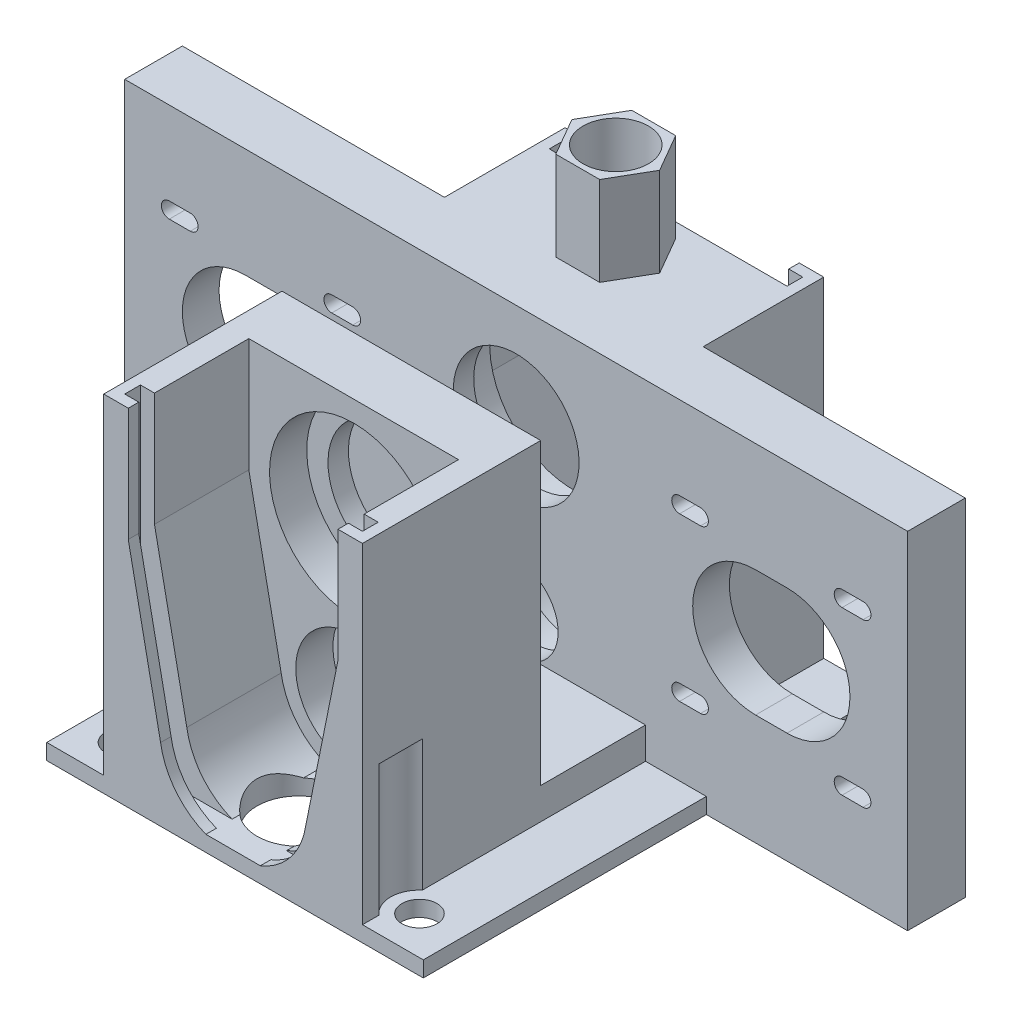
SolidWorks part; units mm, degrees
ref_plane "Front Plane" through (0, 0, 0) normal (0, 0, 1) x (1, 0, 0)
ref_plane "Top Plane" through (0, 0, 0) normal (0, 1, 0) x (1, 0, 0)
ref_plane "Right Plane" through (0, 0, 0) normal (1, 0, 0) x (0, 0, -1)
ref_axis "Axis1" through (88.99, 0, 0) along (-1, 0, 0)
ref_plane "Plane1" through (0, 0, 0) normal (0, 0, -1) x (-1, 0, 0)
ref_plane "Plane2" through (0, 0, 0) normal (0, -1, 0) x (-1, 0, 0)
ref_plane "Plane3" through (0, 0, -42) normal (0, 0, -1) x (-1, 0, 0)
sketch "Sketch2" plane through (0, 0, 0) normal (0, 0, -1) x (-1, 0, 0)
  line L2 (0, 58.0413) -> (0, 28.0413) construction
  line L3 (-24.6785, 78.0413) -> (24.6785, 78.0413)
  line L4 (57.5751, 12.0413) -> (-72.0682, 12.0413) construction
  line L5 (-24.6785, 78.0413) -> (-24.6785, 12.0413)
  line L6 (-24.6785, 12.0413) -> (24.6785, 12.0413)
  line L7 (24.6785, 12.0413) -> (24.6785, 78.0413)
  circle A0 centre (0, 28.0413) radius 11 construction
  circle A1 centre (0, 58.0413) radius 16 construction
  point P4 (0, 58.0413)
  point P6 (0, 28.0413)
  point P7 (20.0824, 64.1811)
  point P8 (15.3009, 32.7193)
  dimension "D1" = 32
  dimension "D2" = 22
  dimension "D6" = 66
  dimension "D3" = 30
  dimension "D5" = 20
  dimension "D4" = 16
extrude "Boss-Extrude1" add sketch "Sketch2" along normal blind 65
ref_plane "Plane5" through (0, 12.0413, 0) normal (0, -1, 0) x (-1, 0, 0)
sketch "Sketch3" plane through (0, 0, 0) normal (0, 0, -1) x (-1, 0, 0)
  line L0 (-24.6785, 12.0413) -> (24.6785, 12.0413) construction
  line L1 (0, 0) -> (0, 102.6324) construction
  circle A0 centre (0, 28.0413) radius 8
  circle A1 centre (0, 58.0413) radius 12
  circle A3 centre (0, 58.0413) radius 16 construction
  circle A4 centre (0, 28.0413) radius 11 construction
  dimension "D1" = 4
  dimension "D2" = 3
  dimension "D4" = 16
  dimension "D5" = 22
  dimension "D6" = 32
  dimension "D3" = 30
extrude "Cut-Extrude1" cut sketch "Sketch3" along normal blind 42
sketch "Sketch5" plane through (0, 0, -42) normal (0, 0, -1) x (-1, 0, 0)
  line L2 (-20, 76.0413) -> (20, 76.0413)
  line L4 (-24.6785, 12.0413) -> (24.6785, 12.0413) construction
  line L6 (13.8042, 25.708) -> (20, 49.5058)
  line L7 (-20, 49.5726) -> (-13.8042, 25.708)
  line L10 (24.6785, 78.0413) -> (-24.6785, 78.0413) construction
  line L11 (-20, 76.0413) -> (-20, 49.5726)
  line L12 (20, 76.0413) -> (20, 49.5058)
  circle A1 centre (0, 58.0413) radius 16 construction
  arc A3 (-13.8042, 25.708) -> (13.8042, 25.708) centre (0, 28.0413) ccw
  dimension "D2" = 16
  dimension "D1" = 14
  dimension "D6" = 32
  dimension "D5" = 2
  dimension "D7" = 30
  dimension "D8" = 20
  dimension "D9" = 20
extrude "Cut-Extrude2" cut sketch "Sketch5" along normal through all
sketch "Sketch6" plane through (0, 0, 0) normal (0, 0, -1) x (-1, 0, 0)
  circle A0 centre (0, 58.0413) radius 16.05
  circle A1 centre (0, 58.0413) radius 12 construction
  circle A2 centre (0, 28.0413) radius 11.05
  circle A3 centre (0, 28.0413) radius 8 construction
  dimension "D1" = 32.1
  dimension "D2" = 22.1
extrude "Cut-Extrude3" cut sketch "Sketch6" along normal blind 7.1
sketch "Sketch7" plane through (0, 0, -42) normal (0, 0, -1) x (-1, 0, 0)
  circle A2 centre (0, 58.0413) radius 16.05
  circle A3 centre (0, 58.0413) radius 16.05
  circle A5 centre (0, 28.0413) radius 11.05
  circle A6 centre (0, 28.0413) radius 11.05
  dimension "D1" = 0
  dimension "D2" = 0
extrude "Cut-Extrude4" cut sketch "Sketch7" against normal blind 7.1
sketch "Sketch8" plane through (0, 0, 0) normal (0, 0, -1) x (-1, 0, 0)
  line L2 (24.6785, 78.0413) -> (-24.6785, 78.0413)
  line L3 (24.6785, 78.0413) -> (24.6785, 12.0413)
  line L4 (24.6785, 12.0413) -> (-24.6785, 12.0413)
  line L5 (-24.6785, 12.0413) -> (-24.6785, 78.0413)
extrude "Boss-Extrude2" add sketch "Sketch8" against normal blind 23
sketch "Sketch9" plane through (0, 0, 0) normal (0, 0, -1) x (-1, 0, 0)
  line L2 (20, 78.0413) -> (-20, 78.0413)
  line L4 (-24.6785, 12.0413) -> (24.6785, 12.0413) construction
  line L5 (20, 78.0413) -> (20, 56.3516)
  line L6 (-20, 56.3516) -> (-13.8326, 25.8825)
  line L7 (13.8326, 25.8825) -> (20, 56.3516)
  line L8 (-20, 78.0413) -> (-20, 56.3516)
  circle A0 centre (0, 56.2822) radius 16 construction
  arc A3 (-13.8326, 25.8825) -> (13.8326, 25.8825) centre (0, 28.0413) ccw
  dimension "D1" = 14
  dimension "D5" = 32
  dimension "D2" = 16
  dimension "D6" = 20
  dimension "D7" = 20
extrude "Cut-Extrude5" cut sketch "Sketch9" against normal through all
ref_plane "Plane4" through (0, 0, -31) normal (0, 0, -1) x (-1, 0, 0)
sketch "Sketch10" plane through (0, 0, -31) normal (0, 0, -1) x (-1, 0, 0)
  line L1 (32.0175, 70.0413) -> (32.0175, 29.2185)
  line L2 (-24.6785, 12.0413) -> (24.6785, 12.0413) construction
  line L5 (-28.9461, 62.8412) -> (-28.9461, 21.0413)
  line L8 (0.9045, 21.0413) -> (-28.9461, 21.0413)
  line L9 (0, 0) -> (0, 85.4363) construction
  line L10 (0.9045, 21.0413) -> (32.0175, 29.2185)
  line L12 (-28.9461, 62.8412) -> (-28.9461, 84.6224)
  line L13 (-28.9461, 84.6224) -> (32.0175, 84.6224)
  line L14 (32.0175, 84.6224) -> (32.0175, 70.0413)
  circle A0 centre (0, 58.0413) radius 10 construction
  circle A1 centre (0, 58.0413) radius 16 construction
  circle A2 centre (0, 28.0413) radius 11 construction
  circle A4 centre (0, 28.0413) radius 4 construction
  dimension "D1" = 32
  dimension "D2" = 22
  dimension "D3" = 30
  dimension "D4" = 20
  dimension "D5" = 8
  dimension "D6" = 16
  dimension "D7" = 7
  dimension "D10" = 7
extrude "Cut-Extrude6" cut sketch "Sketch10" against normal blind 20
sketch "Sketch12" plane through (0, 0, 0) normal (0, 1, 0) x (1, 0, 0)
  circle A0 centre (0, -10.444) radius 8
  ellipse E0 centre (0, -2.444) end of major axis (14, -2.444) minor radius 1.2202 (13.8326, -2.2558) -> (-13.8326, -2.2558) ccw construction
  dimension "D1" = 16
  dimension "D2" = 8
extrude "Cut-Extrude8" cut sketch "Sketch12" along normal up to surface (14.0413 mm away) up to face at (0, 19.9619, 11.5)
sketch "Sketch13" plane through (0, 12.0413, 0) normal (0, -1, 0) x (-1, 0, 0)
  line L2 (24.6785, 11) -> (24.6785, 31)
  line L3 (24.6785, 11) -> (24.6785, 31) construction
  line L4 (24.6785, 31) -> (24.6785, 42)
  line L5 (-24.6785, 65) -> (24.6785, 65) construction
  line L7 (24.6785, 42) -> (74.6785, 42)
  line L8 (97.889, 42) -> (-97.889, 42) construction
  line L9 (74.6785, 42) -> (74.6785, 31)
  line L10 (97.889, 31) -> (-97.889, 31) construction
  line L11 (74.6785, 31) -> (24.6785, 31)
  line L12 (-24.6785, 42) -> (-74.6785, 42)
  line L13 (-24.6785, 65) -> (-24.6785, -23) construction
  line L14 (-74.6785, 42) -> (-74.6785, 31)
  line L15 (-74.6785, 31) -> (-24.6785, 31)
  line L16 (-24.6785, 31) -> (-24.6785, 42)
  dimension "D3" = 50
  dimension "D2" = 23
  dimension "D1" = 0
extrude "Boss-Extrude3" add sketch "Sketch13" against normal up to surface (66 mm away) up to face at (0, 78.0413, -48)
sketch "Sketch15" plane through (0, 0, -42) normal (0, 0, -1) x (-1, 0, 0)
  line L0 (0, 0) -> (0, 87.2744) construction
  line L1 (74.6785, 78.0413) -> (74.6785, 12.0413) construction
  line L2 (25.6785, 66.3413) -> (71.6785, 66.3413)
  line L3 (25.6785, 66.3413) -> (25.6785, 24.0413)
  line L4 (25.6785, 24.0413) -> (71.6785, 24.0413)
  line L5 (71.6785, 66.3413) -> (71.6785, 24.0413)
  line L6 (24.6785, 12.0413) -> (24.6785, 78.0413) construction
  line L7 (-27.1464, 12.0413) -> (27.1464, 12.0413) construction
  line L8 (-71.6785, 66.3413) -> (-71.6785, 24.0413)
  line L9 (-25.6785, 24.0413) -> (-71.6785, 24.0413)
  line L10 (-25.6785, 66.3413) -> (-25.6785, 24.0413)
  line L11 (-25.6785, 66.3413) -> (-71.6785, 66.3413)
  dimension "D1" = 3
  dimension "D2" = 1
  dimension "D3" = 42.3
  dimension "D4" = 12
extrude "Cut-Extrude9" cut sketch "Sketch15" against normal blind 4
sketch "Sketch16" plane through (0, 0, -42) normal (0, 0, -1) x (-1, 0, 0)
  line L0 (-105.1978, 45.1913) -> (88.1587, 45.1913) construction
  line L1 (71.6785, 66.3413) -> (25.6785, 66.3413) construction
  line L2 (25.6785, 24.0413) -> (71.6785, 24.0413) construction
  line L3 (45.6785, 45.1913) -> (51.6785, 45.1913) construction
  line L4 (45.6785, 57.1913) -> (51.6785, 57.1913)
  line L5 (45.6785, 33.1913) -> (51.6785, 33.1913)
  line L6 (48.6785, 83.554) -> (48.6785, 16.5047) construction
  line L7 (25.6785, 66.3413) -> (25.6785, 24.0413) construction
  line L8 (71.6785, 24.0413) -> (71.6785, 66.3413) construction
  line L9 (31.1785, 60.6913) -> (35.1785, 60.6913) construction
  line L10 (31.1785, 62.1913) -> (35.1785, 62.1913)
  line L11 (31.1785, 59.1913) -> (35.1785, 59.1913)
  line L12 (66.1785, 60.6913) -> (62.1785, 60.6913) construction
  line L25 (66.1785, 62.1913) -> (62.1785, 62.1913)
  line L26 (66.1785, 59.1913) -> (62.1785, 59.1913)
  line L27 (31.1785, 29.6913) -> (35.1785, 29.6913) construction
  line L28 (31.1785, 28.1913) -> (35.1785, 28.1913)
  line L29 (31.1785, 31.1913) -> (35.1785, 31.1913)
  line L30 (66.1785, 29.6913) -> (62.1785, 29.6913) construction
  line L31 (66.1785, 28.1913) -> (62.1785, 28.1913)
  line L32 (66.1785, 31.1913) -> (62.1785, 31.1913)
  line L33 (0, 0) -> (0, 89.9864) construction
  line L34 (-45.6785, 45.1913) -> (-51.6785, 45.1913) construction
  line L35 (-45.6785, 57.1913) -> (-51.6785, 57.1913)
  line L36 (-45.6785, 33.1913) -> (-51.6785, 33.1913)
  line L37 (-31.1785, 60.6913) -> (-35.1785, 60.6913) construction
  line L38 (-31.1785, 62.1913) -> (-35.1785, 62.1913)
  line L39 (-31.1785, 59.1913) -> (-35.1785, 59.1913)
  line L40 (-66.1785, 60.6913) -> (-62.1785, 60.6913) construction
  line L41 (-66.1785, 62.1913) -> (-62.1785, 62.1913)
  line L42 (-66.1785, 59.1913) -> (-62.1785, 59.1913)
  line L43 (-31.1785, 29.6913) -> (-35.1785, 29.6913) construction
  line L44 (-31.1785, 28.1913) -> (-35.1785, 28.1913)
  line L45 (-31.1785, 31.1913) -> (-35.1785, 31.1913)
  line L46 (-66.1785, 29.6913) -> (-62.1785, 29.6913) construction
  line L47 (-66.1785, 28.1913) -> (-62.1785, 28.1913)
  line L48 (-66.1785, 31.1913) -> (-62.1785, 31.1913)
  arc A0 (45.6785, 57.1913) -> (45.6785, 33.1913) centre (45.6785, 45.1913) ccw
  arc A1 (51.6785, 33.1913) -> (51.6785, 57.1913) centre (51.6785, 45.1913) ccw
  arc A2 (31.1785, 62.1913) -> (31.1785, 59.1913) centre (31.1785, 60.6913) ccw
  arc A3 (35.1785, 59.1913) -> (35.1785, 62.1913) centre (35.1785, 60.6913) ccw
  arc A16 (66.1785, 62.1913) -> (66.1785, 59.1913) centre (66.1785, 60.6913) cw
  arc A17 (62.1785, 59.1913) -> (62.1785, 62.1913) centre (62.1785, 60.6913) cw
  arc A18 (31.1785, 28.1913) -> (31.1785, 31.1913) centre (31.1785, 29.6913) cw
  arc A19 (35.1785, 31.1913) -> (35.1785, 28.1913) centre (35.1785, 29.6913) cw
  arc A20 (66.1785, 28.1913) -> (66.1785, 31.1913) centre (66.1785, 29.6913) ccw
  arc A21 (62.1785, 31.1913) -> (62.1785, 28.1913) centre (62.1785, 29.6913) ccw
  arc A22 (-45.6785, 57.1913) -> (-45.6785, 33.1913) centre (-45.6785, 45.1913) cw
  arc A23 (-51.6785, 33.1913) -> (-51.6785, 57.1913) centre (-51.6785, 45.1913) cw
  arc A24 (-31.1785, 62.1913) -> (-31.1785, 59.1913) centre (-31.1785, 60.6913) cw
  arc A25 (-35.1785, 59.1913) -> (-35.1785, 62.1913) centre (-35.1785, 60.6913) cw
  arc A26 (-66.1785, 62.1913) -> (-66.1785, 59.1913) centre (-66.1785, 60.6913) ccw
  arc A27 (-62.1785, 59.1913) -> (-62.1785, 62.1913) centre (-62.1785, 60.6913) ccw
  arc A28 (-31.1785, 28.1913) -> (-31.1785, 31.1913) centre (-31.1785, 29.6913) ccw
  arc A29 (-35.1785, 31.1913) -> (-35.1785, 28.1913) centre (-35.1785, 29.6913) ccw
  arc A30 (-66.1785, 28.1913) -> (-66.1785, 31.1913) centre (-66.1785, 29.6913) cw
  arc A31 (-62.1785, 31.1913) -> (-62.1785, 28.1913) centre (-62.1785, 29.6913) cw
  point P8 (48.6785, 45.1913)
  point P14 (33.1785, 60.6913)
  point P28 (64.1785, 60.6913)
  point P36 (33.1785, 29.6913)
  point P43 (64.1785, 29.6913)
  point P52 (-48.6785, 45.1913)
  point P59 (-33.1785, 60.6913)
  point P66 (-64.1785, 60.6913)
  point P73 (-33.1785, 29.6913)
  point P80 (-64.1785, 29.6913)
  dimension "D1" = 12
  dimension "D3" = 31
  dimension "D4" = 1.5
  dimension "D2" = 31
  dimension "D5" = 4
  dimension "D6" = 6
extrude "Cut-Extrude10" cut sketch "Sketch16" against normal up to next
sketch "Sketch17" plane through (0, 78.0413, 0) normal (0, 1, 0) x (1, 0, 0)
  line L0 (0, 55.3583) -> (0, 85.749) construction
  line L1 (-35.5458, 50) -> (45.8299, 50) construction
  line L4 (97.889, 42) -> (-97.889, 42) construction
  line L5 (8.3716, 50) -> (4.1858, 57.25)
  line L6 (4.1858, 57.25) -> (-4.1858, 57.25)
  line L7 (-4.1858, 57.25) -> (-8.3716, 50)
  line L8 (-8.3716, 50) -> (-4.1858, 42.75)
  line L9 (-4.1858, 42.75) -> (4.1858, 42.75)
  line L10 (4.1858, 42.75) -> (8.3716, 50)
  circle A0 centre (0, 50) radius 7.25 construction
  circle A1 centre (0, 50) radius 6.25
  dimension "D2" = 12.5
  dimension "D1" = 14.5
  dimension "D3" = 8
extrude "Boss-Extrude4" add sketch "Sketch17" along normal blind 17
sketch "Sketch18" plane through (0, 78.0413, 0) normal (0, 1, 0) x (1, 0, 0)
  circle A2 centre (0, 50) radius 6.25
  circle A3 centre (0, 50) radius 6.25
  dimension "D1" = 0
extrude "Cut-Extrude11" cut sketch "Sketch18" against normal up to next
sketch "Sketch19" plane through (0, 12.0413, 0) normal (0, -1, 0) x (-1, 0, 0)
  line L0 (-66.3049, 12.556) -> (66.3049, 12.556) construction
  line L1 (0, 76.6155) -> (0, 65) construction
  line L2 (-61.7241, 74.2802) -> (0.6987, 11.8573) construction
  line L4 (13.4481, 26.0042) -> (0, 12.556) construction
  line L7 (-36.2843, 48.8403) -> (-36.2843, -23)
  line L9 (35.556, 48.8403) -> (35.556, -23)
  line L10 (-36.2843, 48.8403) -> (-36.2843, 65)
  line L12 (35.556, 65) -> (35.556, 48.8403)
  line L27 (0, 42) -> (0, -57.588) construction
  line L28 (-25.9179, -13.3619) -> (-763.264, -750.708) construction
  line L29 (-36.2843, 65) -> (35.556, 65)
  line L30 (-36.2843, -23) -> (35.556, -23)
  circle A3 centre (-28.2843, 40.8403) radius 3.3465
  circle A6 centre (28.2843, 40.8403) radius 3.3465
  circle A7 centre (-28.2843, -15.7282) radius 3.3465
  circle A8 centre (28.2843, -15.7282) radius 3.3465
  circle A10 centre (0, -10.444) radius 8
  circle A11 centre (0, -10.444) radius 8
  point P3 (0, 12.556)
  dimension "D2" = 45
  dimension "D1" = 45
  dimension "D5" = 40
  dimension "D6" = 8
  dimension "D3" = 0
extrude "Boss-Extrude5" add sketch "Sketch19" against normal blind 3
sketch "Sketch20" plane through (0, 15.0413, 0) normal (0, 1, 0) x (1, 0, 0)
  circle A0 centre (-28.2843, -15.7282) radius 5.5
  circle A1 centre (28.2843, -15.7282) radius 5.5
  circle A2 centre (28.2843, 40.8403) radius 5.5
  circle A3 centre (-28.2843, 40.8403) radius 5.5
  dimension "D1" = 11
extrude "Cut-Extrude12" cut sketch "Sketch20" along normal blind 25
sketch "Sketch21" plane through (0, 12.0413, 0) normal (0, -1, 0) x (-1, 0, 0)
  circle A0 centre (-28.2843, 40.8403) radius 3.3465
  arc A1 (-25.1451, 42) -> (-31.4234, 42) centre (-28.2843, 40.8403) ccw construction
  circle A2 centre (28.2843, 40.8403) radius 3.3465
  arc A3 (31.4234, 42) -> (25.1451, 42) centre (28.2843, 40.8403) ccw construction
extrude "Cut-Extrude13" cut sketch "Sketch21" against normal up to next
sketch "Sketch22" plane through (0, 0, 0) normal (1, 0, 0) x (0, 0, -1)
  line L0 (63, 78.0413) -> (63, 15.0413)
  line L3 (65, 78.0413) -> (42, 78.0413) construction
  line L7 (44.9934, 15.0413) -> (65, 15.0413) construction
  line L8 (63, 15.0413) -> (65, 15.0413)
  line L9 (65, 78.0413) -> (65, 15.0413) construction
  line L10 (-21, 81.0679) -> (-21, 15.0413)
  line L12 (-23, 15.0413) -> (-19.8814, 15.0413) construction
  line L13 (-21, 15.0413) -> (-23, 15.0413)
  line L14 (-23, 78.0413) -> (-23, 15.0413) construction
  dimension "D1" = 2
  dimension "D2" = 2
sketch "Sketch23" plane through (0, 78.0413, 0) normal (0, 1, 0) x (1, 0, 0)
  line L0 (-24.6785, 65) -> (24.6785, 65) construction
  line L1 (-22.6785, 63) -> (22.6785, 63)
  line L2 (-22.6785, 63) -> (-22.6785, 60)
  line L3 (-22.6785, 60) -> (22.6785, 60)
  line L4 (22.6785, 63) -> (22.6785, 60)
  line L5 (-24.6785, 65) -> (-24.6785, 44.9934) construction
  line L6 (24.6785, 44.9934) -> (24.6785, 65) construction
  line L8 (-22.6785, -18) -> (22.6785, -18)
  line L9 (-22.6785, -18) -> (-22.6785, -21)
  line L10 (-22.6785, -21) -> (22.6785, -21)
  line L11 (22.6785, -18) -> (22.6785, -21)
  line L12 (-24.6785, 11) -> (-24.6785, -23) construction
  line L13 (24.6785, 11) -> (24.6785, -23) construction
  line L14 (5.1962, -23) -> (-5.1962, -23) construction
  point P20 (22.6785, -19.5)
  dimension "D1" = 2
  dimension "D2" = 2
  dimension "D3" = 2
  dimension "D4" = 3
  dimension "D5" = 2
  dimension "D6" = 3
  dimension "D7" = 2
  dimension "D8" = 2
  dimension "D9" = 45.357
  dimension "D10" = 45.357
extrude "Cut-Extrude14" cut sketch "Sketch23" against normal up to surface (63 mm away) up to face at (-27.9886, 15.0413, 2.5761)
sketch "Sketch24" plane through (0, 0, -65) normal (0, 0, -1) x (-1, 0, 0)
  line L0 (24.6785, 78.0413) -> (-24.6785, 78.0413) construction
  line L1 (-20, 76.0413) -> (20, 76.0413)
  line L2 (-20, 76.0413) -> (-20, 78.0413)
  line L3 (-20, 78.0413) -> (20, 78.0413)
  line L4 (20, 76.0413) -> (20, 78.0413)
extrude "Cut-Extrude15" cut sketch "Sketch24" against normal up to next
